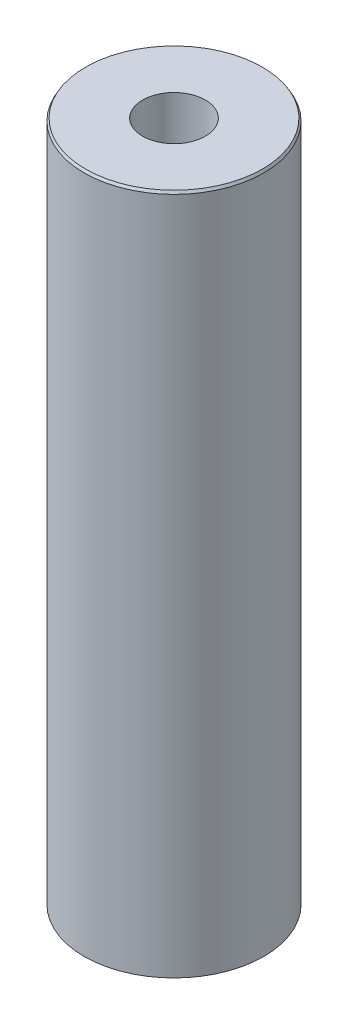
SolidWorks part; units mm, degrees
ref_plane "Front Plane" through (0, 0, 0) normal (0, 0, 1) x (1, 0, 0)
ref_plane "Top Plane" through (0, 0, 0) normal (0, 1, 0) x (1, 0, 0)
ref_plane "Right Plane" through (0, 0, 0) normal (1, 0, 0) x (0, 0, -1)
sketch "Sketch1" plane through (0, 0, 0) normal (0, 1, 0) x (1, 0, 0)
  circle A0 centre (0, 0) radius 37.5
  dimension "SHAFT_OD" = 75
extrude "Boss-Extrude1" add sketch "Sketch1" along normal blind 284.8857
sketch "Sketch2" plane through (0, 0, 0) normal (0, 1, 0) x (1, 0, 0)
  circle A0 centre (0, 0) radius 13.0947
  dimension "BORE_D" = 26.1895
extrude "Cut-Extrude1" cut sketch "Sketch2" along normal through all
chamfer "Chamfer1" distance 1.0641 angle 30 2 edges at (0, 284.8857, 37.5) (0, 0, 37.5) first distance on face at (0, 284.8857, 37.5) first distance on face at (0, 0, 13.0947)
